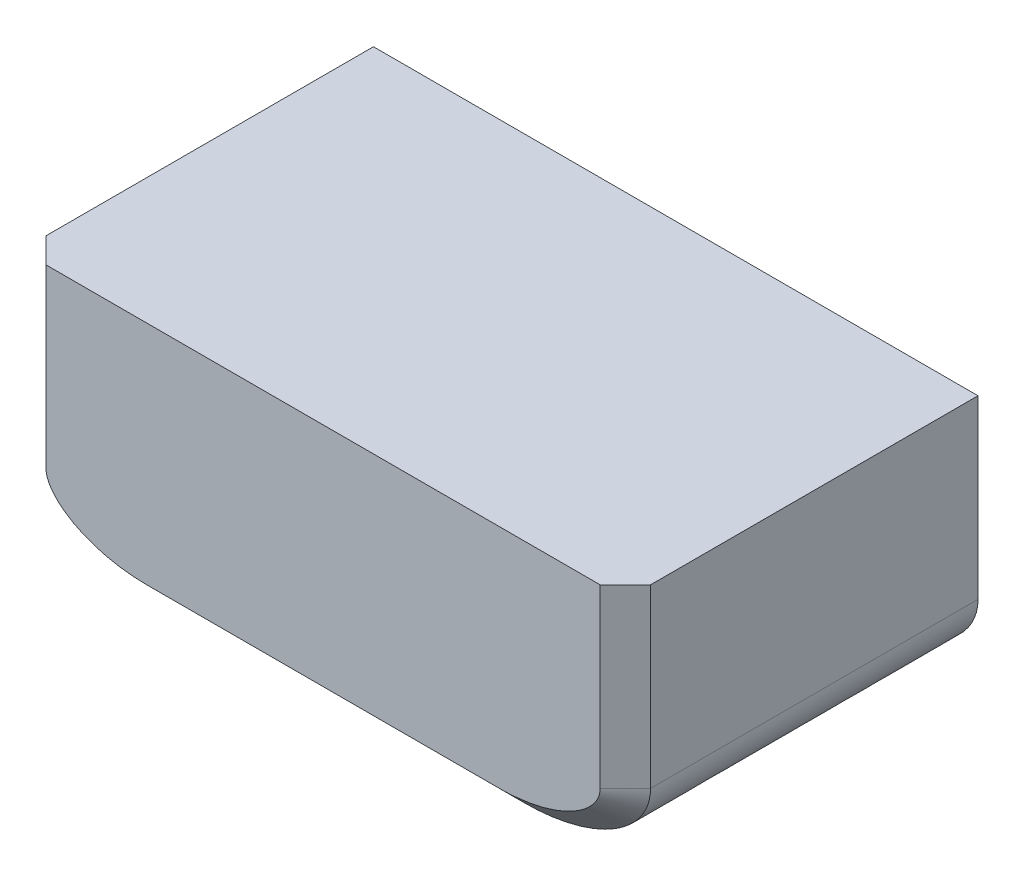
SolidWorks part; units mm, degrees
material "PUR"
ref_plane "Ebene vorne" through (0, 0, 0) normal (0, 0, 1) x (1, 0, 0)
ref_plane "Ebene oben" through (0, 0, 0) normal (0, 1, 0) x (1, 0, 0)
ref_plane "Ebene rechts" through (0, 0, 0) normal (1, 0, 0) x (0, 0, -1)
sketch "Skizze1" plane through (0, 0, 0) normal (0, 0, 1) x (1, 0, 0)
  line L1 (12, -5) -> (-12, -5)
  line L2 (12, -5) -> (12, 5)
  line L3 (12, 5) -> (-12, 5)
  line L4 (-12, -5) -> (-12, 5)
  line L5 (12, -5) -> (-12, 5) construction
  line L6 (12, 5) -> (-12, -5) construction
  point P0 (0, 0)
  dimension "D1" = 10
  dimension "D2" = 24
extrude "Aufsatz-Linear austragen1" add sketch "Skizze1" along normal mid plane 14
hole_wizard "Ø4.0 (4) Durchmesser Bohrung1" positions "Skizze2" profile "Skizze3" hole size "Ø4.0" standard "ISO"
sketch "Skizze2" plane through (0, 0, -7) normal (0, 0, -1) x (-1, 0, 0)
  line L0 (5.5, 0) -> (0, 0) construction
  line L1 (0, 0) -> (-5.5, 0) construction
  point P0 (-5.5, 0)
  point P2 (5.5, 0)
  dimension "D1" = 11
sketch "Skizze3" plane through (5.5, 0, -7) normal (1, 0, 0) x (0, 1, 0)
  line L0 (0, 0) -> (0, 6.2017)
  line L1 (0, 6.2017) -> (2, 5)
  line L2 (2, 5) -> (2, 0)
  line L5 (2, 0) -> (0, 0)
  line L10 (0, 6.2017) -> (-2, 5) construction
  line L11 (0, -6.35) -> (0, 107.95) construction
  dimension "Bohrerdurchmesser" = 4
  dimension "Bohrungstiefe" = 5
  dimension "Spitzenwinkel" = 118
fillet "Verrundung1" radius 3 2 edges at (12, -5, 0) (-12, -5, 0) second distance 5 first distance on face at (12, 0, 0) first distance on face at (-12, 0, 0)
chamfer "Fase2" distance 1 angle 45 5 edges
hole_wizard "M2 Gewindebohrung1" [suppressed] positions "Skizze4" profile "Skizze5" tap size "M2" standard "ISO"
sketch "Skizze4" plane through (0, 0, 7) normal (0, 0, 1) x (1, 0, 0)
  line L0 (5.5, 0) -> (0, 0) construction
  line L1 (0, 0) -> (-5.5, 0) construction
  point P0 (-5.5, 0)
  point P2 (5.5, 0)
  dimension "D1" = 9.5
sketch "Skizze5" plane through (-5.5, 0, 7) normal (1, 0, 0) x (0, -1, 0)
  line L0 (0, 0) -> (0, 5.4807)
  line L1 (0, 5.4807) -> (0.8, 5)
  line L2 (0.8, 5) -> (0.8, 0)
  line L5 (0.8, 0) -> (0, 0)
  line L10 (0, 5.4807) -> (-0.8, 5) construction
  line L11 (0, -6.35) -> (0, 107.95) construction
  dimension "Bohrerdurchmesser" = 1.6
  dimension "Bohrungstiefe" = 5
  dimension "Spitzenwinkel" = 118
cosmetic thread "Bohrungsgewinde1" [suppressed] parameters "D1"=4, "D2"=2
cosmetic thread "Bohrungsgewinde2" [suppressed] parameters "D1"=4, "D2"=2
